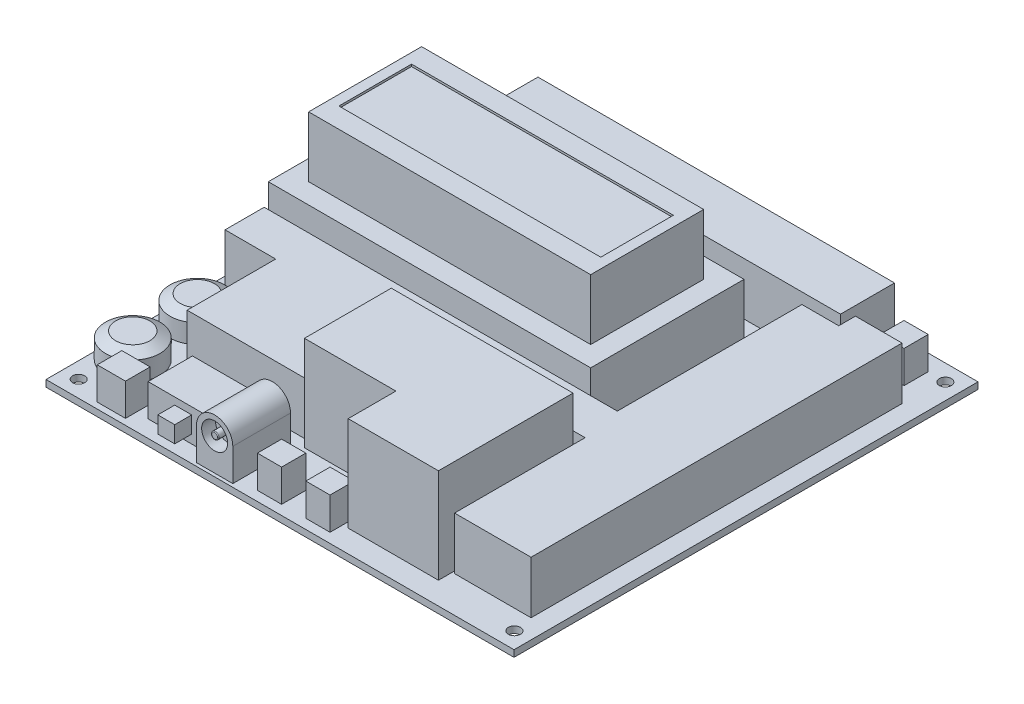
SolidWorks part; units mm, degrees
ref_plane "Front Plane" through (0, 0, 0) normal (0, 0, 1) x (1, 0, 0)
ref_plane "Top Plane" through (0, 0, 0) normal (0, 1, 0) x (1, 0, 0)
ref_plane "Right Plane" through (0, 0, 0) normal (1, 0, 0) x (0, 0, -1)
sketch "Sketch1" plane through (0, 0, 0) normal (0, 1, 0) x (1, 0, 0)
  line L0 (0, 0) -> (0, 33.841) construction
  line L1 (-58, 57.5) -> (58, 57.5)
  line L2 (-58, 57.5) -> (-58, -57.5)
  line L3 (-58, -57.5) -> (58, -57.5)
  line L4 (58, 57.5) -> (58, -57.5)
  line L5 (-58, 57.5) -> (58, -57.5) construction
  line L6 (-58, -57.5) -> (58, 57.5) construction
  line L7 (0, 0) -> (35.7678, 0) construction
  circle A0 centre (54, 53.4) radius 1.5
  circle A1 centre (54, -53.4) radius 1.5
  circle A2 centre (-54, 53.4) radius 1.5
  circle A3 centre (-54, -53.4) radius 1.5
  point P0 (0, 0)
  dimension "D5" = 3
  dimension "D1" = 115
  dimension "D2" = 116
  dimension "D3" = 108
  dimension "D4" = 106.8
sheet metal parameters "Sheet-Metal1" thickness 1.65 parameters "D1"=245.3911
base flange "Base-Flange1" sketch "Sketch1" thickness 1.65 reverse thickness direction yes parameters "D1"=245.3911
sketch "Sketch3" plane through (0, 1.65, 0) normal (0, 1, 0) x (1, 0, 0)
  line L1 (-57.9, 35.5) -> (22, 35.5)
  line L2 (-57.9, 35.5) -> (-57.9, -2.5)
  line L3 (-57.9, -2.5) -> (22, -2.5)
  line L4 (22, 35.5) -> (22, -2.5)
  line L5 (58, 57.5) -> (-58, 57.5) construction
  line L6 (-58, 57.5) -> (-58, -57.5) construction
  dimension "D1" = 22
  dimension "D2" = 60
  dimension "D3" = 80
  dimension "D4" = 0.1
extrude "Extrude1" add sketch "Sketch3" along normal blind 15
sketch "Sketch4" plane through (0, 16.65, 0) normal (0, 1, 0) x (1, 0, 0)
  line L8 (-52.9, 30.5) -> (-52.9, 2.5)
  line L9 (-52.9, 2.5) -> (17, 2.5)
  line L10 (17, 2.5) -> (17, 30.5)
  line L11 (17, 30.5) -> (-52.9, 30.5)
  line L12 (-52.9, 30.5) -> (-52.9, 2.5)
  line L13 (-52.9, 2.5) -> (17, 2.5)
  line L14 (17, 2.5) -> (17, 30.5)
  line L15 (17, 30.5) -> (-52.9, 30.5)
  dimension "D1" = 5
extrude "Extrude2" add sketch "Sketch4" along normal blind 15
sketch "Sketch6" plane through (0, 31.65, 0) normal (0, 1, 0) x (1, 0, 0)
  line L8 (17, 2.5) -> (17, 30.5) construction
  line L9 (-52.9, 30.5) -> (-52.9, 2.5) construction
  line L12 (12, 25.5) -> (-47.9, 25.5)
  line L13 (-47.9, 25.5) -> (-47.9, 7.5)
  line L14 (-47.9, 7.5) -> (12, 7.5)
  line L15 (12, 7.5) -> (12, 25.5)
  line L16 (14.5, 25.5) -> (-50.4, 25.5)
  line L17 (-50.4, 25.5) -> (-50.4, 7.5)
  line L18 (-50.4, 7.5) -> (14.5, 7.5)
  line L19 (14.5, 7.5) -> (14.5, 25.5)
  dimension "D2" = 2.5
  dimension "D3" = 2.5
  dimension "D1" = 5
extrude "Display!" cut sketch "Sketch6" against normal blind 0.53 normal cut yes
sketch "Sketch7" plane through (0, 0, 0) normal (0, -1, 0) x (1, 0, 0)
  line L1 (-57.9, 20.5) -> (33.1, 20.5)
  line L2 (-57.9, 20.5) -> (-57.9, -39.5)
  line L3 (-57.9, -39.5) -> (33.1, -39.5)
  line L4 (33.1, 20.5) -> (33.1, -39.5)
  line L5 (58, -57.5) -> (-58, -57.5) construction
  line L6 (-58, -57.5) -> (-58, 57.5) construction
  dimension "D1" = 91
  dimension "D2" = 60
  dimension "D3" = 18
  dimension "D4" = 0.1
extrude "Wiring Board" add sketch "Sketch7" along normal blind 15
sketch "Sketch8" plane through (0, -15, 0) normal (0, -1, 0) x (1, 0, 0)
  line L0 (-57.9, 20.5) -> (-57.9, -39.5) construction
  line L1 (-43.9, 9.2) -> (-36.9, 9.2)
  line L2 (-43.9, 9.2) -> (-43.9, -10.8)
  line L3 (-43.9, -10.8) -> (-36.9, -10.8)
  line L4 (-36.9, 9.2) -> (-36.9, -10.8)
  line L5 (33.1, 20.5) -> (-57.9, 20.5) construction
  dimension "D1" = 20
  dimension "D2" = 7
  dimension "D3" = 14
  dimension "D4" = 11.3
extrude "Extrude5" add sketch "Sketch8" along normal blind 7.5
sketch "Sketch9" plane through (-58, 0, 0) normal (-1, 0, 0) x (0, 0, 1)
  line L0 (-39.5, -15) -> (-39.5, 0) construction
  line L1 (-29.5, -3.1) -> (-19, -3.1)
  line L2 (-29.5, -3.1) -> (-29.5, -11.6)
  line L3 (-29.5, -11.6) -> (-19, -11.6)
  line L4 (-19, -3.1) -> (-19, -11.6)
  line L5 (20.5, -15) -> (-39.5, -15) construction
  line L6 (-27, -5.6) -> (-21.5, -5.6)
  line L7 (-21.5, -5.6) -> (-21.5, -9.1)
  line L8 (-27, -9.1) -> (-21.5, -9.1)
  line L9 (-27, -5.6) -> (-27, -9.1)
  point P4 (-39.5, -7.5)
  dimension "D1" = 8.5
  dimension "D2" = 10.5
  dimension "D3" = 10
  dimension "D4" = 3.4
  dimension "D5" = 2.5
extrude "USB" cut sketch "Sketch9" against normal blind 7.5 normal cut yes
chamfer "Chamfer1" distance 2 angle 45 2 edges at (-54.2, -3.1, -19) (-54.2, -3.1, -29.5)
sketch "Sketch10" plane through (0, 1.65, 0) normal (0, 1, 0) x (1, 0, 0)
  line L0 (-58, 57.5) -> (-58, -57.5) construction
  line L1 (-58, -57.5) -> (58, -57.5) construction
  circle A0 centre (-51.5, -26.5) radius 6.75
  circle A1 centre (-51.5, -42.5) radius 6.75
  dimension "D1" = 13.5
  dimension "D3" = 16
  dimension "D2" = 6.5
  dimension "D4" = 15
extrude "Potentiometers" add sketch "Sketch10" along normal blind 6.2
sketch "Sketch11" plane through (0, 1.65, 0) normal (0, 1, 0) x (1, 0, 0)
  line L0 (-26.092, -53.3) -> (-23.1, -53.3)
  line L1 (-46.8, -49.9) -> (-39.8, -49.9)
  line L2 (-46.8, -49.9) -> (-46.8, -56)
  line L3 (-46.8, -56) -> (-39.8, -56)
  line L4 (-39.8, -49.9) -> (-39.8, -56)
  line L5 (-36.9, -42.3) -> (-23.1, -42.3)
  line L6 (-36.9, -42.3) -> (-36.9, -53.3)
  line L7 (-36.9, -53.3) -> (-30.292, -53.3)
  line L8 (-23.1, -42.3) -> (-23.1, -53.3)
  line L10 (-30.292, -53.3) -> (-30.292, -57.5)
  line L11 (-30.292, -57.5) -> (-26.092, -57.5)
  line L12 (-26.092, -53.3) -> (-26.092, -57.5)
  line L13 (-21.5, -42.4) -> (-12.5, -42.4)
  line L14 (-21.5, -42.4) -> (-21.5, -56.7)
  line L15 (-21.5, -56.7) -> (-12.5, -56.7)
  line L16 (-12.5, -42.4) -> (-12.5, -56.7)
  line L17 (-8, -49.1) -> (-2, -49.1)
  line L18 (-8, -49.1) -> (-8, -55.1)
  line L19 (-8, -55.1) -> (-2, -55.1)
  line L20 (-2, -49.1) -> (-2, -55.1)
  line L21 (4, -49.1) -> (10, -49.1)
  line L22 (4, -49.1) -> (4, -55.1)
  line L23 (4, -55.1) -> (10, -55.1)
  line L24 (10, -49.1) -> (10, -55.1)
  line L25 (-58, -44.32) -> (-58, -57.5) construction
  line L26 (-58, -57.5) -> (58, -57.5) construction
  line L27 (-58, -28.32) -> (-58, -40.68) construction
  line L28 (-58, 57.5) -> (-58, -24.68) construction
  line L29 (58, 57.5) -> (-58, 57.5) construction
  line L30 (43.66, 53.5) -> (49.66, 53.5)
  line L31 (43.66, 53.5) -> (43.66, 47.5)
  line L32 (43.66, 47.5) -> (49.66, 47.5)
  line L33 (49.66, 53.5) -> (49.66, 47.5)
  line L34 (58, -57.5) -> (58, 57.5) construction
  line L35 (-58, 57.5) -> (-58, -24.68) construction
  line L36 (-55.82, 47.8) -> (-53.82, 47.8)
  line L37 (-55.82, 47.8) -> (-55.82, 42.8)
  line L38 (-55.82, 42.8) -> (-53.82, 42.8)
  line L39 (-53.82, 47.8) -> (-53.82, 42.8)
  line L40 (-53.52, 47.8) -> (-51.52, 47.8)
  line L41 (-53.52, 47.8) -> (-53.52, 42.8)
  line L42 (-53.52, 42.8) -> (-51.52, 42.8)
  line L43 (-51.52, 47.8) -> (-51.52, 42.8)
  dimension "D1" = 7
  dimension "D2" = 13.8
  dimension "D3" = 11
  dimension "D4" = 7.6
  dimension "D5" = 11.2
  dimension "D6" = 1.5
  dimension "D7" = 21.1
  dimension "D8" = 4.2
  dimension "D9" = 9
  dimension "D10" = 14.3
  dimension "D11" = 36.5
  dimension "D12" = 0.8
  dimension "D13" = 6
  dimension "D14" = 2.4
  dimension "D15" = 50
  dimension "D16" = 6
  dimension "D17" = 4
  dimension "D18" = 8.34
  dimension "D19" = 2.18
  dimension "D20" = 2
  dimension "D21" = 0.3
  dimension "D22" = 5
  dimension "D23" = 14.7
extrude "Keep Accessible!!" add sketch "Sketch11" along normal blind 8
sketch "Sketch12" plane through (0, 1.65, 0) normal (0, 1, 0) x (1, 0, 0)
  line L0 (-48.9486, 53.6703) -> (-48.9486, 44.8322)
  line L1 (-48.9486, 44.8322) -> (-35.8339, 44.8322)
  line L2 (-35.8339, 44.8322) -> (-35.8339, 41.9811)
  line L3 (-35.8339, 41.9811) -> (37.2945, 41.9811)
  line L4 (37.2945, 41.9811) -> (39.4328, 41.9811)
  line L5 (39.4328, 41.9811) -> (39.4328, 53.6703)
  line L6 (39.4328, 53.6703) -> (39.4328, 55.3809)
  line L7 (39.4328, 55.3809) -> (-48.9486, 55.3809)
  line L8 (-48.9486, 55.3809) -> (-48.9486, 53.6703)
  line L9 (41.7136, 43.4066) -> (41.7136, 39.2727)
  line L10 (41.7136, 39.2727) -> (32.5904, 39.2727)
  line L11 (32.5904, 39.2727) -> (32.5904, -6.4861)
  line L12 (32.5904, -6.4861) -> (-54.9357, -6.4861)
  line L13 (-54.9357, -6.4861) -> (-54.9357, -16.1795)
  line L14 (-54.9357, -16.1795) -> (-42.3912, -16.1795)
  line L15 (-42.3912, -16.1795) -> (-42.3912, -38.1323)
  line L16 (-42.3912, -38.1323) -> (-13.3109, -38.1323)
  line L17 (-13.3109, -38.1323) -> (-13.3109, -16.1795)
  line L18 (-13.3109, -16.1795) -> (34.301, -16.1795)
  line L19 (34.301, -16.1795) -> (34.301, -48.5385)
  line L20 (34.301, -48.5385) -> (53.2602, -48.5385)
  line L21 (53.2602, -48.5385) -> (53.2602, 43.4066)
  line L22 (53.2602, 43.4066) -> (41.7136, 43.4066)
extrude "Extrude9" add sketch "Sketch12" along normal blind 13
sketch "Sketch13" plane through (0, 1.65, 0) normal (0, 1, 0) x (1, 0, 0)
  line L0 (-11.3152, -18.6028) -> (-11.3152, -40.128)
  line L1 (-11.3152, -40.128) -> (11.3503, -40.128)
  line L2 (11.3503, -40.128) -> (11.3503, -51.9597)
  line L3 (11.3503, -51.9597) -> (33.7308, -51.9597)
  line L4 (33.7308, -51.9597) -> (33.7308, -18.6028)
  line L5 (33.7308, -18.6028) -> (-11.3152, -18.6028)
extrude "Hot! Voltage Regs" add sketch "Sketch13" along normal blind 23.5
sketch "Sketch14" plane through (0, 0, 56.7) normal (0, 0, 1) x (1, 0, 0)
  line L0 (-21.5, 9.65) -> (-12.5, 9.65) construction
  circle A0 centre (-17, 9.65) radius 4.5
extrude "Extrude10" add sketch "Sketch14" against normal up to surface (14.3 mm away) up to face at (-17, 5.65, 42.4)
sketch "Sketch15" plane through (0, 0, 56.7) normal (0, 0, 1) x (1, 0, 0)
  line L0 (-36.9, 1.65) -> (-30.292, 1.65) construction
  line L1 (-31.1638, 10.5463) -> (-25.2139, 10.5463)
  line L2 (-31.1638, 10.5463) -> (-31.1638, 7.9077)
  line L3 (-31.1638, 7.9077) -> (-25.2139, 7.9077)
  line L4 (-25.2139, 10.5463) -> (-25.2139, 7.9077)
  line L5 (-31.1638, 1.65) -> (-25.2139, 1.65)
  line L6 (-31.1638, 1.65) -> (-31.1638, 3.783)
  line L7 (-31.1638, 3.783) -> (-25.2139, 3.783)
  line L8 (-25.2139, 1.65) -> (-25.2139, 3.783)
  circle A0 centre (-17, 9.65) radius 3.2198
  circle A1 centre (-17, 9.65) radius 0.8963
extrude "Extrude11" cut sketch "Sketch15" against normal up to surface (3.4 mm away) and the other way blind 10 normal cut yes up to face at (-33.596, 5.65, 53.3)
fillet "Fillet1" radius 0.2 5 edges at (-57.9, -5.6, -24.25) (-57.9, -7.35, -21.5) (-57.9, -9.1, -24.25) (-57.9, -7.35, -27) (-17.8963, 9.65, 56.7)
chamfer "Chamfer2" distance 1.5 distance2 2.5 2 edges at (-51.5, 7.85, 33.25) (-51.5, 7.85, 49.25) first distance on face at (-51.5, 7.85, 33.25) first distance on face at (-51.5, 7.85, 49.25)
flat pattern "Flat-Pattern1" [suppressed]
sketch "Bend-Lines1" plane through (0, 0, 0) normal (0, 1, 0) x (-1, 0, 0)
